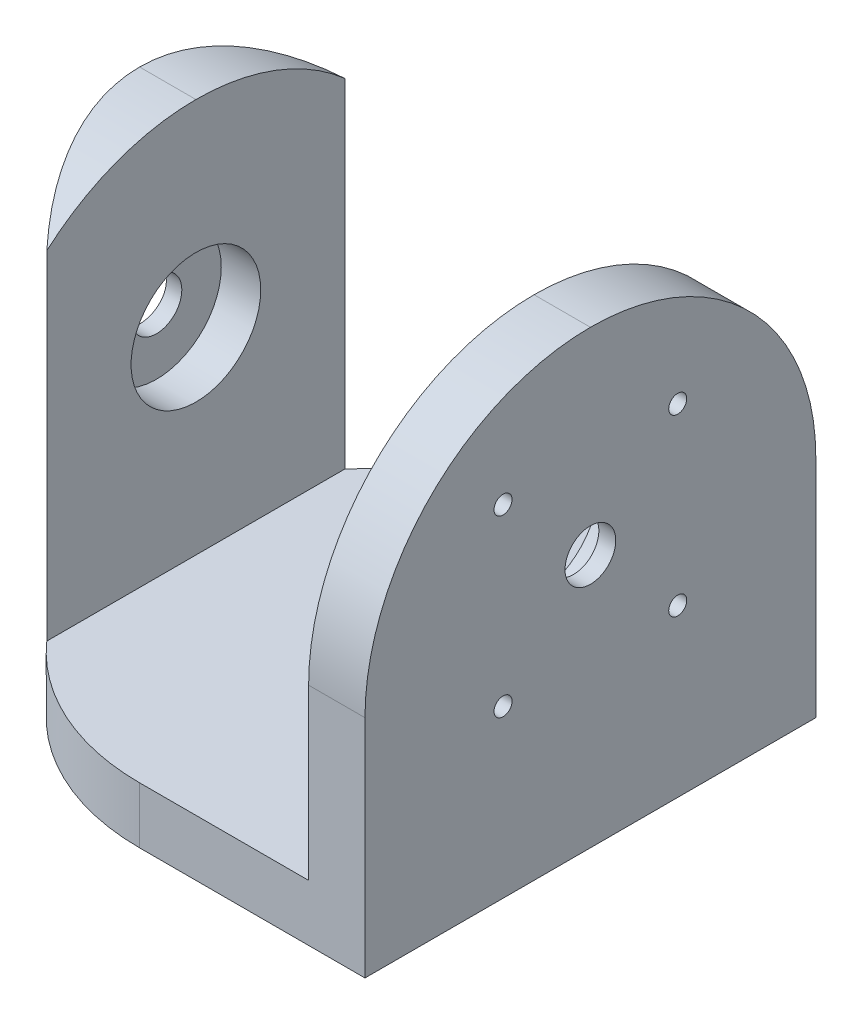
SolidWorks part; units mm, degrees
ref_plane "Front Plane" through (0, 0, 0) normal (0, 0, 1) x (1, 0, 0)
ref_plane "Top Plane" through (0, 0, 0) normal (0, 1, 0) x (1, 0, 0)
ref_plane "Right Plane" through (0, 0, 0) normal (1, 0, 0) x (0, 0, -1)
sketch "Sketch1" plane through (0, 0, 0) normal (0, 1, 0) x (1, 0, 0)
  line L1 (-40, -40) -> (40, -40)
  line L2 (-40, -40) -> (-40, 40)
  line L3 (-40, 40) -> (40, 40)
  line L4 (40, -40) -> (40, 40)
  line L5 (-40, -40) -> (40, 40) construction
  line L6 (-40, 40) -> (40, -40) construction
  point P0 (0, 0)
  dimension "D1" = 80
  dimension "D2" = 80
extrude "Boss-Extrude1" add sketch "Sketch1" along normal blind 10
sketch "Sketch2" plane through (0, 10, 0) normal (0, 1, 0) x (1, 0, 0)
  line L0 (-40, -40) -> (40, -40) construction
  line L1 (40, 40) -> (30, 40)
  line L2 (40, 40) -> (40, -40)
  line L3 (40, -40) -> (30, -40)
  line L4 (30, 40) -> (30, -40)
  dimension "D1" = 10
extrude "Boss-Extrude2" add sketch "Sketch2" along normal blind 70
sketch "Sketch4" plane through (40, 0, 0) normal (1, 0, 0) x (0, 0, -1)
  line L1 (-15.5, 60.5) -> (15.5, 60.5)
  line L2 (-15.5, 60.5) -> (-15.5, 29.5)
  line L3 (-15.5, 29.5) -> (15.5, 29.5)
  line L4 (15.5, 60.5) -> (15.5, 29.5)
  line L5 (-40, 80) -> (40, 80) construction
  line L6 (40, 80) -> (40, 0) construction
  circle A0 centre (0, 35) radius 12.5
  dimension "D5" = 25
  dimension "D1" = 31
  dimension "D2" = 31
  dimension "D3" = 19.5
  dimension "D4" = 24.5
hole_wizard "CSK for M3 Countersunk Flat Head Screw1" positions "Sketch5" profile "Sketch6" countersink size "M3" standard "ISO" end condition through all
sketch "Sketch5" plane through (30, 0, 0) normal (-1, 0, 0) x (0, 0, 1)
  point P0 (-15.5, 60.5)
  point P3 (15.5, 60.5)
  point P6 (15.5, 29.5)
  point P9 (-15.5, 29.5)
sketch "Sketch6" plane through (30, 60.5, -15.5) normal (0, 1, 0) x (0, 0, 1)
  line L0 (0, 0) -> (0, 10)
  line L1 (0, 10) -> (1.6, 10)
  line L2 (1.6, 10) -> (1.6, 1.55)
  line L3 (1.6, 1.55) -> (3.15, 0)
  line L5 (3.15, 0) -> (0, 0)
  line L6 (-1.6, 1.55) -> (-3.15, 0) construction
  line L11 (0, -6.35) -> (0, 107.95) construction
  dimension "Thru Hole Dia." = 3.2
  dimension "Thru Hole Depth" = 10
  dimension "Near C'Sink Dia." = 6.3
  dimension "Near C'Sink Angle" = 90
sketch "Sketch8" plane through (0, 10, 0) normal (0, 1, 0) x (1, 0, 0)
  line L1 (-15.5, 15.5) -> (15.5, 15.5)
  line L2 (-15.5, 15.5) -> (-15.5, -15.5)
  line L3 (-15.5, -15.5) -> (15.5, -15.5)
  line L4 (15.5, 15.5) -> (15.5, -15.5)
  line L5 (-15.5, 15.5) -> (15.5, -15.5) construction
  line L6 (-15.5, -15.5) -> (15.5, 15.5) construction
  point P0 (0, 0)
  dimension "D1" = 31
  dimension "D2" = 31
ref_plane "Plane1" through (0, 0, 0) normal (1, 0, 0) x (0, 0, -1)
mirror "Mirror1" about plane through (0, 0, 0) normal (1, 0, 0) of "Boss-Extrude2"
sketch "Sketch11" plane through (0, 10, 0) normal (0, 1, 0) x (1, 0, 0)
  line L0 (2.281, -1.75) -> (-2.281, -1.75)
  circle A0 centre (0, 0) radius 2.875
  dimension "D1" = 5.75
  dimension "D2" = 1.75
extrude "Cut-Extrude2" cut sketch "Sketch11" against normal through all contours L0 A0 region at (0, 10, -0.3535)
sketch "Sketch7" plane through (40, 0, 0) normal (1, 0, 0) x (0, 0, -1)
  line L0 (-40, 80) -> (40, 80) construction
  circle A0 centre (0, 45) radius 11.5
  dimension "D1" = 23
  dimension "D2" = 35
extrude "Cut-Extrude1" cut sketch "Sketch7" against normal through all
fillet "Fillet2" radius 40 4 edges at (35, 80, -40) (35, 80, 40) (-35, 80, 40) (-35, 80, -40)
sketch "Sketch12" plane through (0, 0, 0) normal (0, -1, 0) x (1, 0, 0)
  line L0 (2.281, 1.75) -> (-2.281, 1.75) construction
  line L1 (2.281, 1.75) -> (-2.281, 1.75)
  line L4 (40, -40) -> (40, 40)
  line L5 (40, 40) -> (-40, 40)
  line L7 (-40, -40) -> (40, -40)
  line L8 (40, -40) -> (40, 40)
  line L9 (40, 40) -> (-40, 40)
  line L11 (-40, -40) -> (40, -40)
  line L13 (-40, 40) -> (-40, -40)
  line L14 (-40, 40) -> (-40, -40)
  arc A0 (-2.281, 1.75) -> (2.281, 1.75) centre (0, 0) ccw construction
  arc A1 (-2.281, 1.75) -> (2.281, 1.75) centre (0, 0) ccw
  circle A2 centre (0, 0) radius 3.625
  arc M13 (2.281, 1.75) -> (-2.281, 1.75) centre (0, 0) cw
  line M14 (-2.281, 1.75) -> (2.281, 1.75)
  dimension "D2" = 7.25
  dimension "D1" = 0
extrude "Boss-Extrude3" add sketch "Sketch12" along normal blind 10 contours A2 M14 M13 region at (-3.5225, 0, 0)
sketch "Sketch14" plane through (-30, 0, 0) normal (1, 0, 0) x (0, 0, -1)
  circle A0 centre (0, 45) radius 11.5 construction
  circle A1 centre (0, 45) radius 11.5
  circle A2 centre (0, 45) radius 4.5
  dimension "D1" = 9
extrude "Boss-Extrude4" add sketch "Sketch14" along normal blind 3 from offset 10 offset against normal yes
sketch "Sketch13" plane through (0, 0, 0) normal (0, -1, 0) x (-1, 0, 0)
  line L1 (40, 40) -> (-40, 40)
  line L2 (40, 40) -> (40, -40)
  line L3 (40, -40) -> (-40, -40)
  line L4 (-40, 40) -> (-40, -40)
  line L5 (40, 40) -> (-40, -40) construction
  line L6 (40, -40) -> (-40, 40) construction
  circle A0 centre (0, 0) radius 40
  line M4 (40, -40) -> (40, 40)
  line M5 (40, 40) -> (-40, 40)
extrude "Cut-Extrude4" cut sketch "Sketch13" against normal through all contours A0 L3 M4 | A0 L2 M5 region at (-31.0653, 0, -31.0653) region at (-31.0653, 0, 31.0653)
sketch "Sketch15" plane through (30, 0, 0) normal (-1, 0, 0) x (0, 0, 1)
  circle A0 centre (0, 45) radius 4.5 construction
  circle A1 centre (0, 45) radius 11.5
  circle A2 centre (0, 45) radius 11.5
  circle A3 centre (0, 45) radius 4.5
  dimension "D1" = 0
extrude "Boss-Extrude5" add sketch "Sketch15" along normal blind 3 from surface starting at face at (40, 45, -11.5)
